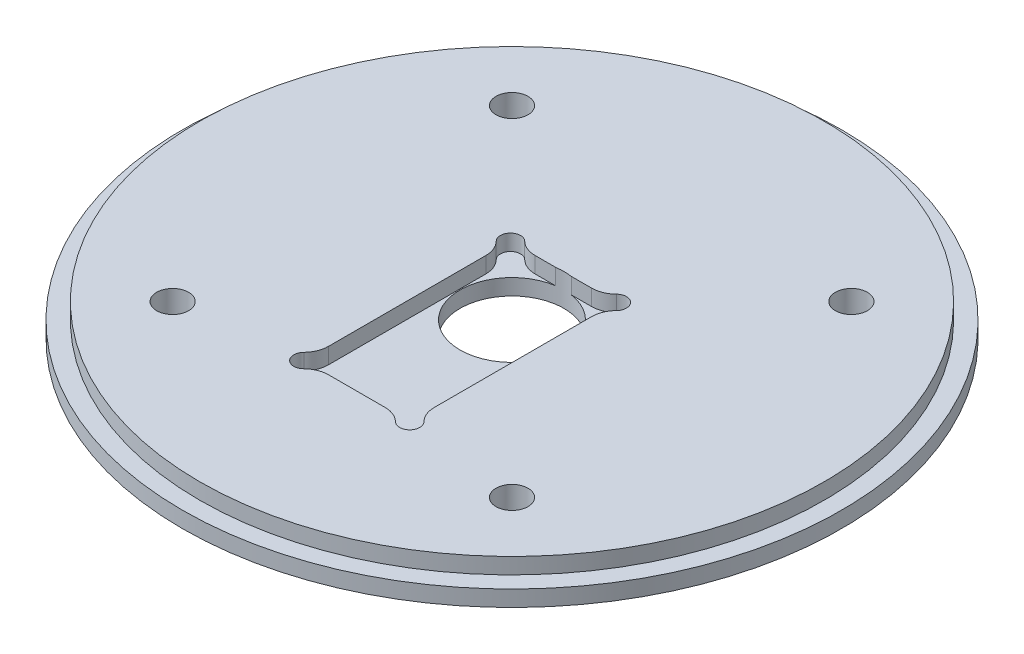
SolidWorks part; units mm, degrees
ref_plane "Front Plane" through (0, 0, 0) normal (0, 0, 1) x (1, 0, 0)
ref_plane "Top Plane" through (0, 0, 0) normal (0, 1, 0) x (1, 0, 0)
ref_plane "Right Plane" through (0, 0, 0) normal (1, 0, 0) x (0, 0, -1)
sketch "Sketch2" plane through (0, 0, 0) normal (0, 1, 0) x (1, 0, 0)
  circle A0 centre (0, 0) radius 65.405
  dimension "D1" = 130.81
extrude "Boss-Extrude1" add sketch "Sketch2" along normal blind 6.35
sketch "Sketch4" plane through (0, 6.35, 0) normal (0, 1, 0) x (1, 0, 0)
  circle A0 centre (0, 0) radius 61.976
  circle A1 centre (0, 0) radius 65.405 construction
  circle A2 centre (0, 0) radius 65.405
  dimension "D1" = 123.952
extrude "Cut-Extrude1" cut sketch "Sketch4" against normal blind 3.175
sketch "Sketch5" plane through (0, 6.35, 0) normal (0, 1, 0) x (1, 0, 0)
  line L0 (33.676, 33.676) -> (-33.676, -33.676) construction
  line L1 (-33.676, 33.676) -> (33.676, -33.676) construction
  line L2 (-1000, 0) -> (49000, 0) construction
  point P1 (-33.676, -33.676)
  point P2 (33.676, 33.676)
  point P5 (33.676, -33.676)
  point P6 (-33.676, 33.676)
  dimension "D1" = 95.25
  dimension "D2" = 45
hole_wizard "1/4 (0.25) Diameter Hole1" positions "Sketch5" profile "Sketch6" hole size "1/4" standard "ANSI Inch" end condition through all
sketch "Sketch6" plane through (-33.676, 6.35, -33.676) normal (1, 0, 0) x (0, 0, 1)
  line L0 (0, 0) -> (0, 6.35)
  line L1 (0, 6.35) -> (3.175, 6.35)
  line L2 (3.175, 6.35) -> (3.175, 0)
  line L5 (3.175, 0) -> (0, 0)
  line L11 (0, -6.35) -> (0, 107.95) construction
  dimension "Thru Hole Dia." = 6.35
  dimension "Thru Hole Depth" = 6.35
sketch "Sketch7" plane through (0, 6.35, 0) normal (0, 1, 0) x (1, 0, 0)
  point P0 (0, 0)
hole_wizard "13/16 (0.8125) Diameter Hole1" positions "Sketch7" profile "Sketch8" hole size "13/16" standard "ANSI Inch" end condition through all
sketch "Sketch8" plane through (0, 6.35, 0) normal (1, 0, 0) x (0, 0, 1)
  line L0 (0, 0) -> (0, 6.35)
  line L1 (0, 6.35) -> (10.3187, 6.35)
  line L2 (10.3187, 6.35) -> (10.3187, 0)
  line L5 (10.3187, 0) -> (0, 0)
  line L11 (0, -6.35) -> (0, 107.95) construction
  dimension "Thru Hole Dia." = 20.6375
  dimension "Thru Hole Depth" = 6.35
sketch "Sketch11" plane through (0, 6.35, 0) normal (0, 1, 0) x (1, 0, 0)
  line L0 (0, -3.4925) -> (0, 3.4925) construction
  line L1 (-5.601, 10.2) -> (5.601, 10.2)
  line L2 (-10.5, 5.301) -> (-10.5, -25.901)
  line L3 (-5.601, -30.8) -> (5.601, -30.8)
  line L4 (10.5, 5.301) -> (10.5, -25.901)
  line L5 (-10.5, 10.2) -> (10.5, -30.8) construction
  line L6 (-10.5, -30.8) -> (10.5, 10.2) construction
  line L7 (0, -10.3) -> (7.6415, -10.3) construction
  line L8 (-10.5, -30.8) -> (-8.5, -30.8) construction
  line L9 (-10.5, -28.8) -> (-10.5, -30.8) construction
  line L10 (-10.5, 10.2) -> (-8.5, 10.2) construction
  line L11 (-10.5, 10.2) -> (-10.5, 8.2) construction
  line L12 (8.5, -30.8) -> (10.5, -30.8) construction
  line L13 (10.5, -28.8) -> (10.5, -30.8) construction
  line L14 (8.5, 10.2) -> (10.5, 10.2) construction
  line L15 (10.5, 10.2) -> (10.5, 8.2) construction
  arc A0 (-11.9286, -29.4003) -> (-9.1003, -32.2286) centre (-10.5, -30.8) ccw
  arc A1 (11.9286, -29.4003) -> (9.1003, -32.2286) centre (10.5, -30.8) cw
  arc A2 (11.9286, 8.8003) -> (9.1003, 11.6286) centre (10.5, 10.2) ccw
  arc A3 (-11.9286, 8.8003) -> (-9.1003, 11.6286) centre (-10.5, 10.2) cw
  arc A4 (-11.9286, -29.4003) -> (-10.5, -25.901) centre (-15.5, -25.901) ccw
  arc A5 (-9.1003, -32.2286) -> (-5.601, -30.8) centre (-5.601, -35.8) cw
  arc A6 (11.9286, -29.4003) -> (10.5, -25.901) centre (15.5, -25.901) cw
  arc A7 (9.1003, -32.2286) -> (5.601, -30.8) centre (5.601, -35.8) ccw
  arc A8 (11.9286, 8.8003) -> (10.5, 5.301) centre (15.5, 5.301) ccw
  arc A9 (9.1003, 11.6286) -> (5.601, 10.2) centre (5.601, 15.2) cw
  arc A10 (-9.1003, 11.6286) -> (-5.601, 10.2) centre (-5.601, 15.2) ccw
  arc A11 (-11.9286, 8.8003) -> (-10.5, 5.301) centre (-15.5, 5.301) cw
  point P0 (0, 0)
  point P1 (0, -10.3)
  dimension "D4" = 2
  dimension "D5" = 5
  dimension "D1" = 10.2
  dimension "D2" = 21
  dimension "D3" = 41
extrude "Cut-Extrude3" cut sketch "Sketch11" against normal blind 3.175
sketch "Sketch9" plane through (0, 0, 0) normal (0, -1, 0) x (1, 0, 0)
  circle A0 centre (-33.676, -33.676) radius 3.175 construction
  circle A1 centre (33.676, -33.676) radius 3.175 construction
  circle A2 centre (33.676, 33.676) radius 3.175 construction
  circle A3 centre (-33.676, 33.676) radius 3.175 construction
  circle A4 centre (-33.676, -33.676) radius 3.175 construction
  circle A5 centre (33.676, -33.676) radius 3.175 construction
  circle A6 centre (33.676, 33.676) radius 3.175 construction
  circle A7 centre (-33.676, 33.676) radius 3.175 construction
  circle A8 centre (-33.676, 33.676) radius 6.0325
  circle A9 centre (33.676, 33.676) radius 6.0325
  circle A10 centre (33.676, -33.676) radius 6.0325
  circle A11 centre (-33.676, -33.676) radius 6.0325
  point P13 (-33.676, 33.676)
  point P14 (33.676, 33.676)
  point P15 (33.676, -33.676)
  point P16 (-33.676, -33.676)
  dimension "D1" = 12.065
extrude "Cut-Extrude2" cut sketch "Sketch9" against normal blind 1.5875
equation "\"AIRFRAME_OD\"= 5.15in"
equation "\"AIRFRAME_ID\"= 5.00in"
equation "\"FLAT_T\"= 0.125in"
equation "\"NOSE_EXP_L\"= 27in"
equation "\"NOSE_SHOULDER_L\"= 5in"
equation "\"MAIN_L\"= 30in"
equation "\"RECO_COUP_L\"= 10in"
equation "\"RECO_SWITCH_L\"= 2in"
equation "\"DROGUE_L\"= 20in"
equation "\"ATS_FORE_COUP_L\"= 5.5in"
equation "\"ATS_AFT_COUP_L\"= 4.5in"
equation "\"LOWER_L\"= 30in"
equation "\"FIN_N\"= 4"
equation "\"CR_AFT_X\"= 0.5in"
equation "\"CR_FORE_X\"= 9.25in"
equation "\"D1@Boss-Extrude1\"=2*\"FLAT_T\""
equation "\"COUPLER_OD\"= 4.998in"
equation "\"COUPLER_ID\"= 4.88in"
equation "\"RECO_ROD_X\"= 3.5in"
equation "\"ATS_ROD_X\"= 3.75in"
equation "\"FIN_ROOT\"= 8in"
equation "\"FIN_X\"= 0.75in"
equation "\"MOTOR_OD\"= 3.091in"
equation "\"MOTOR_ID\"= 3.00in"
equation "\"MOTOR_L\"= 14in"
equation "\"MOTOR_LOWER_X\"= 2in"
equation "\"D1@Sketch4\"=\"COUPLER_ID\""
equation "\"D1@Cut-Extrude1\"=\"FLAT_T\""
equation "\"D1@Cut-Extrude3\"=\"FLAT_T\""
equation "\"D1@Sketch2\"=\"AIRFRAME_OD\""
equation "\"D1@Sketch5\"=\"ATS_ROD_X\""
